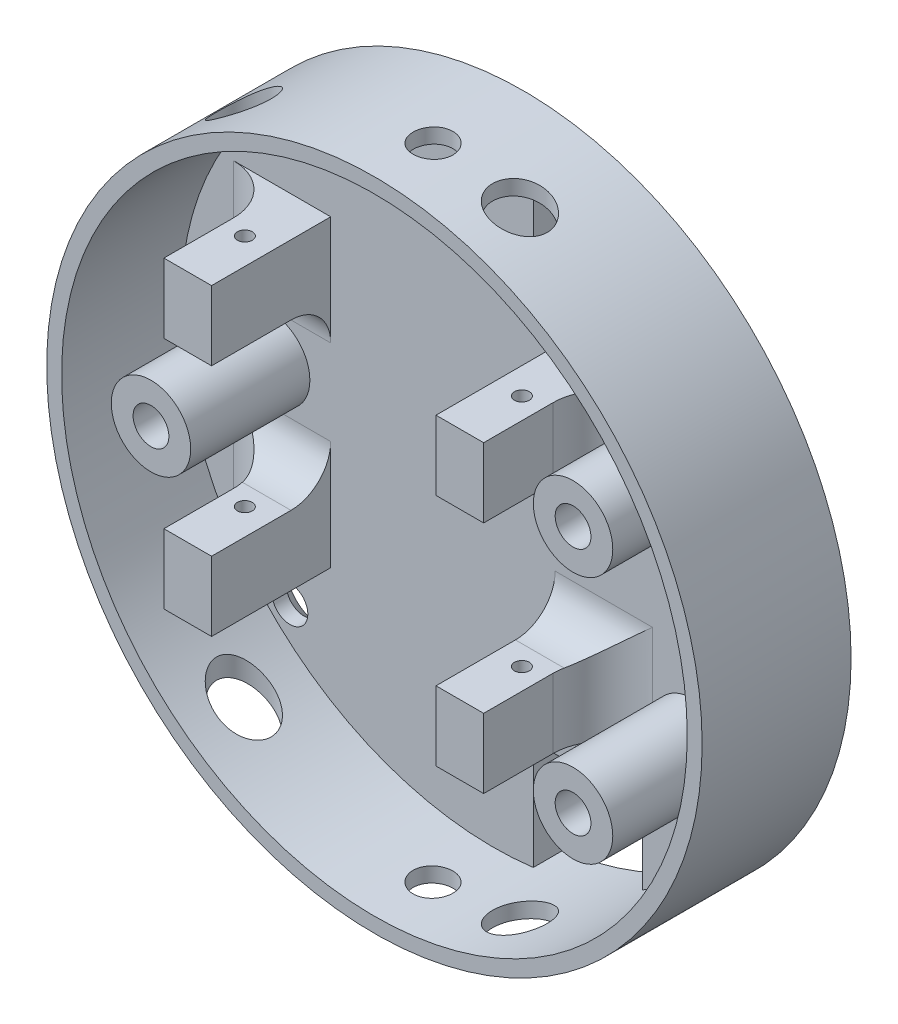
SolidWorks part; units mm, degrees
material "PEI"
ref_plane "Alzado" through (0, 0, 0) normal (0, 0, 1) x (1, 0, 0)
ref_plane "Planta" through (0, 0, 0) normal (0, 1, 0) x (1, 0, 0)
ref_plane "Vista lateral" through (0, 0, 0) normal (1, 0, 0) x (0, 0, -1)
sketch "Croquis1" plane through (0, 0, 0) normal (0, 0, 1) x (1, 0, 0)
  circle A0 centre (0, 0) radius 33
  dimension "D1" = 66
extrude "Saliente-Extruir1" add sketch "Croquis1" along normal blind 3
sketch "Croquis2" plane through (0, 0, 3) normal (0, 0, 1) x (1, 0, 0)
  line L0 (-21.2, -15.3) -> (-16.4, -15.3)
  line L1 (11, -15.3) -> (6.2, -15.3)
  line L2 (-21.2, -15.3) -> (-21.2, -8.3)
  line L3 (-21.2, -8.3) -> (-16.4, -8.3)
  line L4 (-16.4, -8.3) -> (-16.4, -15.3)
  line L5 (6.2, -15.3) -> (6.2, -8.3)
  line L6 (6.2, -8.3) -> (11, -8.3)
  line L7 (11, -8.3) -> (11, -15.3)
  line L8 (6.2, -15.3) -> (11, -15.3)
  line L9 (0, 0) -> (12.8027, 0) construction
  line L10 (11, 8.3) -> (11, 15.3)
  line L11 (11, 15.3) -> (6.2, 15.3)
  line L12 (6.2, 8.3) -> (11, 8.3)
  line L13 (6.2, 15.3) -> (6.2, 8.3)
  line L14 (-16.4, 8.3) -> (-16.4, 15.3)
  line L15 (-21.2, 15.3) -> (-16.4, 15.3)
  line L16 (-21.2, 15.3) -> (-21.2, 8.3)
  line L17 (-21.2, 8.3) -> (-16.4, 8.3)
  point P2 (0, -15.3)
  point P3 (-16.4, -15.3)
  point P13 (8.6, -15.3)
  point P16 (8.6, 15.3)
  dimension "D1" = 32.2
  dimension "D2" = 11
  dimension "D4" = 4.8
  dimension "D5" = 4.8
  dimension "D6" = 15.3
  dimension "D7" = 7
  dimension "D3" = 7
extrude "Saliente-Extruir2" add sketch "Croquis2" along normal blind 12 contours L7 L6 L5 L1 | L4 L3 L2 L0 | L16 L17 L14 L15 | L11 L13 L12 L10 region at (-18.8, -11.8, 3) region at (8.6, -11.8, 3) region at (8.6, 11.8, 3) region at (-18.8, 11.8, 3)
sketch "Croquis3" plane through (0, -15.3, 0) normal (0, -1, 0) x (1, 0, 0)
  line L0 (-21.2, 15) -> (-21.2, 3) construction
  line L3 (11, 15) -> (11, 3) construction
  line L6 (-21.2, 3) -> (-16.4, 3) construction
  circle A0 centre (-19.05, 9) radius 0.75
  circle A1 centre (8.85, 9) radius 0.75
  dimension "D1" = 1.5
  dimension "D2" = 2.15
  dimension "D3" = 2.15
  dimension "D4" = 6
extrude "Cortar-Extruir1" cut sketch "Croquis3" against normal up to surface (30.6 mm away) up to face at (8.6, 15.3, 9)
ref_plane "Plano1" through (0, -33, 0) normal (0, -1, 0) x (-1, 0, 0)
ref_plane "Plano2" through (0, -29.45, 0) normal (0, -1, 0) x (-1, 0, 0)
sketch "Croquis6" plane through (0, 0, 0) normal (0, 0, -1) x (-1, 0, 0)
  line L0 (-20.5061, 20.5061) -> (0, 0) construction
  line L1 (0, 0) -> (0, -33) construction
  circle A0 centre (-20, 12.5) radius 1.8
  circle A1 centre (-20, -12.5) radius 1.8
  circle A2 centre (22.5, 0) radius 1.8
  circle A3 centre (0, 0) radius 29 construction
  circle A4 centre (0, 0) radius 33 construction
  circle A5 centre (-20.5061, 20.5061) radius 1.8
  circle A6 centre (20.5061, 20.5061) radius 1.8
  circle A7 centre (20.5061, -20.5061) radius 1.8
  circle A8 centre (-20.5061, -20.5061) radius 1.8
  point P24 (0, 0)
  dimension "D1" = 3.6
  dimension "D2" = 3.6
  dimension "D3" = 3.6
  dimension "D10" = 3.6
  dimension "D6" = 25
  dimension "D7" = 12.5
  dimension "D4" = 22.5
  dimension "D5" = 20
  dimension "D8" = 4
  dimension "D9" = 135
  dimension "D11" = 4
extrude "Cortar-Extruir4" cut sketch "Croquis6" against normal up to surface (3 mm away) up to face at (-18.8, -11.8, 3)
sketch "Croquis7" plane through (0, 0, 3) normal (0, 0, 1) x (1, 0, 0)
  circle A2 centre (0, 0) radius 33 construction
  circle A9 centre (0, 0) radius 33
  circle A11 centre (0, 0) radius 31.5
  dimension "D1" = 1.5
extrude "Saliente-Extruir3" add sketch "Croquis7" along normal blind 12
ref_plane "Plano3" through (0, -33, 0) normal (0, -1, 0) x (-1, 0, 0)
sketch "Croquis8" plane through (0, -33, 0) normal (0, -1, 0) x (-1, 0, 0)
  line L0 (-33, -15) -> (33, -15) construction
  circle A1 centre (-8.75, -9.1) radius 2.75
  circle A3 centre (19.05, -9.1) radius 2.75
  circle A4 centre (0, -9.1) radius 2
  dimension "D1" = 4
  dimension "D5" = 5.5
  dimension "D6" = 5.5
  dimension "D2" = 5.9
  dimension "D3" = 8.75
  dimension "D4" = 19.05
extrude "Cortar-Extruir5" cut sketch "Croquis8" against normal blind 14
sketch "Croquis9" plane through (0, 0, 3) normal (0, 0, 1) x (1, 0, 0)
  circle A0 centre (20, -12.5) radius 1.8 construction
  circle A1 centre (20, -12.5) radius 1.8
  circle A2 centre (-22.5, 0) radius 1.8 construction
  circle A3 centre (-22.5, 0) radius 1.8
  circle A4 centre (20, 12.5) radius 1.8 construction
  circle A5 centre (20, 12.5) radius 1.8
  circle A6 centre (-22.5, 0) radius 4
  circle A7 centre (20, -12.5) radius 4
  circle A8 centre (20, 12.5) radius 4
  dimension "D1" = 8
extrude "Saliente-Extruir4" add sketch "Croquis9" along normal up to surface (12 mm away) up to face at (33, 0, 15)
sketch "Sketch3" plane through (0, 0, 0) normal (0, 0, -1) x (-1, 0, 0)
  line L1 (4.1, -7.6) -> (-4.1, -7.6)
  line L2 (4.1, -7.6) -> (4.1, 7.6)
  line L3 (4.1, 7.6) -> (-4.1, 7.6)
  line L4 (-4.1, -7.6) -> (-4.1, 7.6)
  line L5 (4.1, -7.6) -> (-4.1, 7.6) construction
  line L6 (4.1, 7.6) -> (-4.1, -7.6) construction
  point P0 (0, 0)
  dimension "D1" = 8.2
  dimension "D2" = 15.2
extrude "Cut-Extrude1" cut sketch "Sketch3" against normal blind 0.5
hole_wizard "Avellanado para tornillo con cabeza plana de M31" positions "Sketch4" profile "Sketch5" countersink size "M3" standard "Ansi Metric" end condition through all
sketch "Sketch4" plane through (0, 0, 0) normal (0, 0, -1) x (-1, 0, 0)
  point P0 (-20, 12.5)
  point P3 (-20, -12.5)
  point P6 (22.5, 0)
sketch "Sketch5" plane through (20, 12.5, 0) normal (1, 0, 0) x (0, 1, 0)
  line L0 (0, 0) -> (0, 15)
  line L1 (0, 15) -> (1.8, 15)
  line L2 (1.8, 15) -> (1.8, 1.35)
  line L3 (1.8, 1.35) -> (3.15, 0)
  line L5 (3.15, 0) -> (0, 0)
  line L6 (-1.8, 1.35) -> (-3.15, 0) construction
  line L11 (0, -6.35) -> (0, 107.95) construction
  dimension "Thru Hole Dia." = 3.6
  dimension "Thru Hole Depth" = 15
  dimension "Near C'Sink Dia." = 6.3
  dimension "Near C'Sink Angle" = 90
mirror "Mirror1" about plane through (0, 0, 0) normal (0, 1, 0) of "Cortar-Extruir5"
fillet "Fillet5" radius 4 4 edges at (-18.8, 8.3, 3) (8.6, 8.3, 3) (8.6, -8.3, 3) (-18.8, -8.3, 3)
fillet "Fillet6" radius 5 4 edges at (-21.2, 9.8, 3) (-21.2, -9.8, 3) (11, 9.8, 3) (11, -9.8, 3)
sketch "Sketch9" plane through (0, 0, 0) normal (0, 0, -1) x (-1, 0, 0)
  line L0 (-4, -31.245) -> (-4, -20.245)
  line L1 (-4, -20.245) -> (-7, -20.245)
  line L2 (-15, -22.7993) -> (-15, -27.6993)
  line L4 (-7, -20.245) -> (-7, -22.7993)
  line L5 (-7, -22.7993) -> (-15, -22.7993)
  arc A0 (-4, -31.245) -> (-15, -27.6993) centre (0, 0) cw
  dimension "D2" = 11
  dimension "D1" = 31.5
  dimension "D6" = 4.9
  dimension "D9" = 8.4457
  dimension "D3" = 15
  dimension "D4" = 8
  dimension "D5" = 3
extrude "Cut-Extrude4" cut sketch "Sketch9" against normal up to surface (3 mm away) up to face at (31.5, 0, 3)
sketch "Sketch10" plane through (0, 0, 0) normal (0, 0, -1) x (-1, 0, 0)
  line L0 (-7, -22.7993) -> (-15, -22.7993) construction
  line L1 (-4, -22.7993) -> (3.1, -22.7993)
  line L2 (-4, -22.7993) -> (-4, -30.8993)
  line L3 (-4, -30.8993) -> (3.1, -30.8993)
  line L4 (3.1, -22.7993) -> (3.1, -30.8993)
  line L5 (-4, -22.7993) -> (3.1, -30.8993) construction
  line L6 (-4, -30.8993) -> (3.1, -22.7993) construction
  line L7 (-4, -31.245) -> (-4, -20.245) construction
  line L8 (0, 0) -> (-11.9554, 0) construction
  line L9 (-4, 30.8993) -> (3.1, 22.7993) construction
  line L10 (-4, 22.7993) -> (3.1, 30.8993) construction
  line L11 (3.1, 22.7993) -> (3.1, 30.8993)
  line L12 (-4, 30.8993) -> (3.1, 30.8993)
  line L13 (-4, 22.7993) -> (-4, 30.8993)
  line L14 (-4, 22.7993) -> (3.1, 22.7993)
  point P0 (-0.45, -26.8493)
  point P16 (-0.45, 26.8493)
  dimension "D1" = 7.1
  dimension "D2" = 8.1
extrude "Cut-Extrude5" cut sketch "Sketch10" against normal blind 0.4
mirror "Mirror3" about plane through (0, 0, 0) normal (0, 1, 0) of "Cut-Extrude4"
hole_wizard "Refrentado para tornillo tapón con cabeza plana de clavija de M31" positions "Croquis10" profile "Croquis11" countersink size "M3" standard "Ansi Metric" end condition up to next
sketch "Croquis10" plane through (0, 0, 0) normal (0, 0, -1) x (-1, 0, 0)
  point P0 (-20.5061, -20.5061)
  point P3 (20.5061, -20.5061)
  point P6 (20.5061, 20.5061)
  point P9 (-20.5061, 20.5061)
sketch "Croquis11" plane through (20.5061, -20.5061, 0) normal (1, 0, 0) x (0, 1, 0)
  line L0 (0, 0) -> (0, 15)
  line L1 (0, 15) -> (1.8, 15)
  line L2 (1.8, 15) -> (1.8, 1.56)
  line L3 (1.8, 1.56) -> (3.36, 0)
  line L5 (3.36, 0) -> (0, 0)
  line L6 (-1.8, 1.56) -> (-3.36, 0) construction
  line L11 (0, -6.35) -> (0, 107.95) construction
  dimension "Diámetro de taladro hasta el siguiente" = 3.6
  dimension "Profundidad de taladro hasta el siguiente" = 15
  dimension "Diámetro de avellanado cercano" = 6.72
  dimension "Ángulo de avellanado cercano" = 90
equation "\"D2@Croquis6\"=\"D1@Croquis6\""
equation "\"D3@Croquis6\"=\"D1@Croquis6\""
equation "\"D7@Croquis6\"=\"D6@Croquis6\"/2"
equation "\"D6@Croquis8\"=\"D5@Croquis8\""
equation "\"D3@Croquis2\"=\"D7@Croquis2\""
equation "\"D1@Sketch9\"=63/2"
